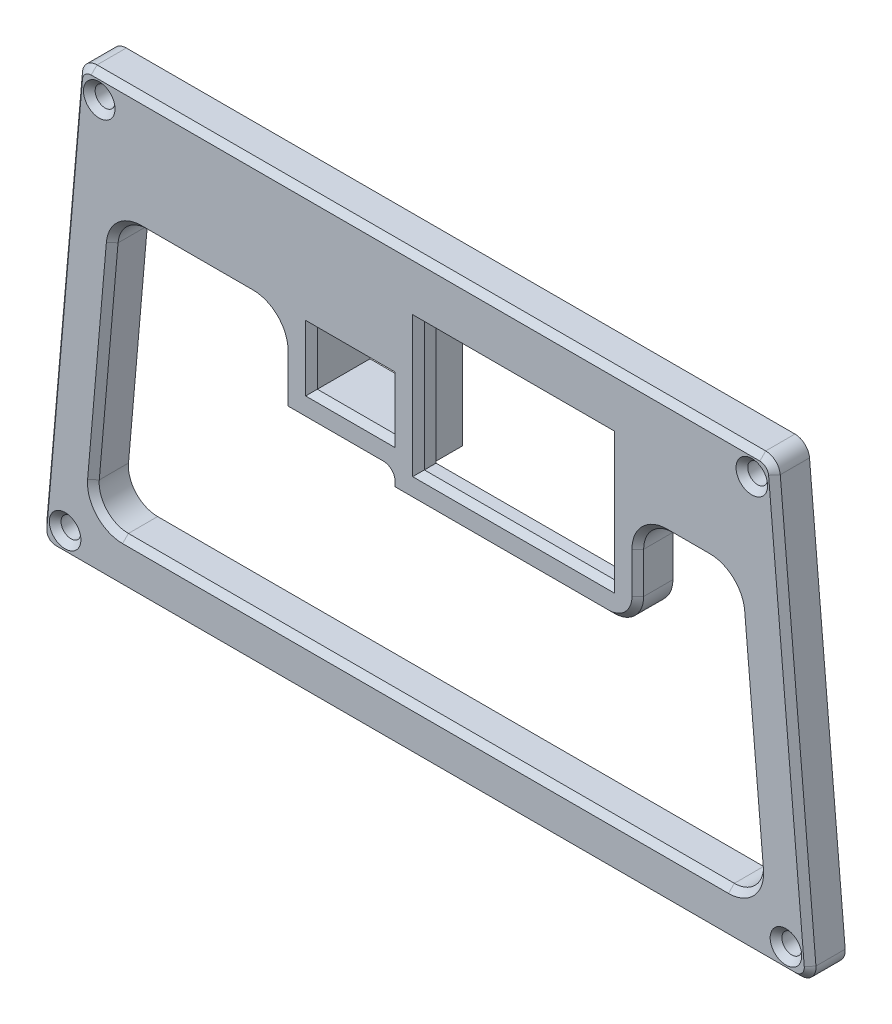
SolidWorks part; units mm, degrees
ref_plane "Front Plane" through (0, 0, 0) normal (0, 0, 1) x (1, 0, 0)
ref_plane "Top Plane" through (0, 0, 0) normal (0, 1, 0) x (1, 0, 0)
ref_plane "Right Plane" through (0, 0, 0) normal (1, 0, 0) x (0, 0, -1)
ref_plane "Plane1" through (0, 0, 3) normal (0, 0, 1) x (1, 0, 0)
sketch "Sketch1" plane through (0, 0, 3) normal (0, 0, 1) x (1, 0, 0)
  line L0 (-43.5313, 89.6442) -> (-43.5313, 121.6442)
  line L1 (-43.5313, 121.6442) -> (-81.0313, 121.6442)
  line L2 (-81.0313, 121.6442) -> (-81.0313, 89.6442)
  line L3 (-81.0313, 89.6442) -> (-43.5313, 89.6442)
extrude "Boss-Extrude1" add sketch "Sketch1" against normal blind 3
sketch "Sketch2" plane through (-43.5313, 0, 0) normal (1, 0, 0) x (0, 0, -1)
  line L0 (-3, 121.6442) -> (3, 121.6442)
  line L1 (3, 121.6442) -> (3, 59.9296)
  line L2 (3, 59.9296) -> (-3, 59.9296)
  line L3 (-3, 59.9296) -> (-3, 121.6442)
extrude "Boss-Extrude2" add sketch "Sketch2" along normal blind 25.6627
sketch "Sketch3" plane through (0, 121.6442, 0) normal (0, 1, 0) x (-1, 0, 0)
  line L0 (81.0313, -3) -> (17.8686, -3)
  line L1 (17.8686, -3) -> (17.8686, 3)
  line L2 (17.8686, 3) -> (81.0313, 3)
  line L3 (81.0313, 3) -> (81.0313, -3)
extrude "Boss-Extrude3" add sketch "Sketch3" along normal blind 5
sketch "Sketch4" plane through (0, 59.9296, 0) normal (0, -1, 0) x (1, 0, 0)
  line L0 (-81.0313, -3) -> (-81.0313, 3)
  line L1 (-81.0313, 3) -> (-17.8686, 3)
  line L2 (-17.8686, 3) -> (-17.8686, -3)
  line L3 (-17.8686, -3) -> (-81.0313, -3)
extrude "Boss-Extrude4" add sketch "Sketch4" along normal blind 8
sketch "Sketch5" plane through (-81.0313, 0, 0) normal (-1, 0, 0) x (0, 0, 1)
  line L0 (3, 126.6442) -> (3, 51.9296)
  line L1 (3, 51.9296) -> (-3, 51.9296)
  line L2 (-3, 51.9296) -> (-3, 126.6442)
  line L3 (-3, 126.6442) -> (3, 126.6442)
extrude "Boss-Extrude5" add sketch "Sketch5" along normal blind 55.7639
sketch "Sketch6" plane through (-81.0313, 0, 0) normal (1, 0, 0) x (0, 0, -1)
  line L0 (0, 89.6442) -> (-3, 89.6442)
  line L1 (-3, 89.6442) -> (-3, 59.9296)
  line L2 (-3, 59.9296) -> (3, 59.9296)
  line L3 (3, 59.9296) -> (3, 92.4442)
  line L4 (3, 92.4442) -> (0, 92.4442)
  line L5 (0, 92.4442) -> (0, 89.6442)
extrude "Cut-Extrude1" cut sketch "Sketch6" against normal blind 2.5
sketch "Sketch7" plane through (-83.5313, 0, 0) normal (1, 0, 0) x (0, 0, -1)
  line L0 (3, 92.4442) -> (-3, 92.4442)
  line L1 (-3, 92.4442) -> (-3, 59.9296)
  line L2 (-3, 59.9296) -> (3, 59.9296)
  line L3 (3, 59.9296) -> (3, 92.4442)
extrude "Cut-Extrude2" cut sketch "Sketch7" against normal blind 18.3
sketch "Sketch8" plane through (-43.5313, 0, 0) normal (-1, 0, 0) x (0, 0, 1)
  line L0 (3, 89.6442) -> (-3, 89.6442)
  line L1 (-3, 89.6442) -> (-3, 59.9296)
  line L2 (-3, 59.9296) -> (3, 59.9296)
  line L3 (3, 59.9296) -> (3, 89.6442)
extrude "Cut-Extrude3" cut sketch "Sketch8" against normal blind 2.5
sketch "Sketch9" plane through (-41.0313, 0, 0) normal (-1, 0, 0) x (0, 0, 1)
  line L0 (-3, 106.6442) -> (-3, 59.9296)
  line L1 (-3, 59.9296) -> (3, 59.9296)
  line L2 (3, 59.9296) -> (3, 106.6442)
  line L3 (3, 106.6442) -> (-3, 106.6442)
extrude "Cut-Extrude4" cut sketch "Sketch9" against normal blind 20.969
sketch "Sketch10" plane through (-101.8313, 0, 0) normal (1, 0, 0) x (0, 0, -1)
  line L0 (3, 59.9296) -> (3, 106.6442)
  line L1 (3, 106.6442) -> (-3, 106.6442)
  line L2 (-3, 106.6442) -> (-3, 59.9296)
  line L3 (-3, 59.9296) -> (3, 59.9296)
extrude "Cut-Extrude5" cut sketch "Sketch10" against normal blind 32.7701
sketch "Sketch11" plane through (0, 0, -3) normal (0, 0, -1) x (-1, 0, 0)
  line L0 (101.8313, 92.4442) -> (81.0313, 92.4442)
  line L1 (81.0313, 92.4442) -> (81.0313, 111.6442)
  line L2 (81.0313, 111.6442) -> (101.8313, 111.6442)
  line L3 (101.8313, 111.6442) -> (101.8313, 92.4442)
extrude "Boss-Extrude6" add sketch "Sketch11" along normal blind 4
sketch "Sketch12" plane through (0, 0, 3) normal (0, 0, 1) x (1, 0, 0)
  line L0 (-46.0313, 116.6442) -> (-78.5313, 116.6442)
  line L1 (-78.5313, 116.6442) -> (-78.5313, 94.6442)
  line L2 (-78.5313, 94.6442) -> (-46.0313, 94.6442)
  line L3 (-46.0313, 94.6442) -> (-46.0313, 116.6442)
extrude "Cut-Extrude6" cut sketch "Sketch12" against normal through all
sketch "Sketch13" plane through (0, 0, 3) normal (0, 0, 1) x (1, 0, 0)
  line L0 (-96.8313, 106.6442) -> (-96.8313, 97.4442)
  line L1 (-96.8313, 97.4442) -> (-83.5313, 97.4442)
  line L2 (-83.5313, 97.4442) -> (-83.5313, 106.6442)
  line L3 (-83.5313, 106.6442) -> (-96.8313, 106.6442)
extrude "Cut-Extrude7" cut sketch "Sketch13" against normal through all
draft "Draft1" type of draft neutral plane draft angle 5 faces to draft 2 face at (-20.0623, 83.2869, 0) face at (-134.6014, 83.2869, 0) neutral plane through (0, 59.9296, 0) neutral plane normal (0, 1, 0) reverse direction yes parameters "D1"=5
draft "Draft2" type of draft neutral plane draft angle 5 faces to draft 2 face at (-136.7952, 89.2869, 0) face at (-17.8686, 89.2869, 0) neutral plane through (0, 126.6442, 0) neutral plane normal (0, 1, 0) parameters "D1"=5
hole_wizard "#4 Clearance Hole1" positions "Sketch15" profile "Sketch14" hole size "#4" standard "ANSI Inch"
sketch "Sketch15" plane through (0, 0, 3) normal (0, 0, 1) x (1, 0, 0)
  point P0 (-21.5339, 122.6442)
  point P1 (-133.1299, 122.6442)
  point P2 (-138.9666, 55.9296)
  point P3 (-15.6971, 55.9296)
sketch "Sketch14" plane through (-21.5339, 122.6442, 3) normal (1, 0, 0) x (0, -1, 0)
  line L0 (0, 0) -> (0, 10)
  line L1 (0, 10) -> (1.7, 10)
  line L2 (1.7, 10) -> (1.7, 0)
  line L5 (1.7, 0) -> (0, 0)
  line L11 (0, -6.35) -> (0, 107.95) construction
  dimension "Thru Hole Dia." = 3.4
  dimension "Thru Hole Depth" = 10
fillet "Fillet1" radius 1 3 edges at (-83.5313, 92.4442, 1.5) (-83.5313, 89.6442, 1.5) (-101.8313, 92.4442, -2) tangent propagation no
fillet "Fillet2" radius 2.5 4 edges at (-11.3319, 51.9296, 0) (-143.3319, 51.9296, 0) (-17.8686, 126.6442, 0) (-136.7952, 126.6442, 0) tangent propagation no
fillet "Fillet3" radius 5 7 edges at (-101.8313, 106.6442, 0) (-41.0313, 106.6442, 0) (-41.0313, 89.6442, 0) (-20.0623, 59.9296, 0) (-24.1493, 106.6442, 0) (-130.5144, 106.6442, 0) (-134.6014, 59.9296, 0) tangent propagation no
chamfer "Chamfer1" distance 1 angle 45 40 edges at (-83.5313, 91.0442, 3) (-83.8242, 92.1513, 3) (-92.6813, 92.4442, 3) (-83.2384, 89.9371, 3) (-101.5384, 92.7371, 3) (-64.2813, 89.6442, 3) (-42.4958, 91.1087, 3) (-41.0313, 98.1442, 3) (-39.5668, 105.1797, 3) (-32.3811, 106.6442, 3) (-101.8313, 97.5442, 3) (-25.3531, 105.3306, 3) (-103.2958, 105.1797, 3) (-22.144, 83.7227, 3) (-116.382, 106.6442, 3) (-21.8325, 61.5516, 3) (-129.3107, 105.3306, 3) (-77.3319, 59.9296, 3) (-132.5198, 83.7227, 3) (-132.8313, 61.5516, 3) (-131.4299, 122.6442, 3) (-78.5313, 105.6442, 3) (-62.2813, 116.6442, 3) (-62.2813, 94.6442, 3) (-46.0313, 105.6442, 3) (-90.1813, 97.4442, 3) (-96.8313, 102.0442, 3) (-83.5313, 102.0442, 3) (-90.1813, 106.6442, 3) (-13.9971, 55.9296, 3) (-77.3319, 51.9296, 3) (-142.4468, 52.7406, 3) (-12.217, 52.7406, 3) (-140.0445, 89.5048, 3) (-14.6193, 89.5048, 3) (-136.1933, 125.9874, 3) (-18.4704, 125.9874, 3) (-77.3319, 126.6442, 3) (-19.8339, 122.6442, 3) (-137.2666, 55.9296, 3)
